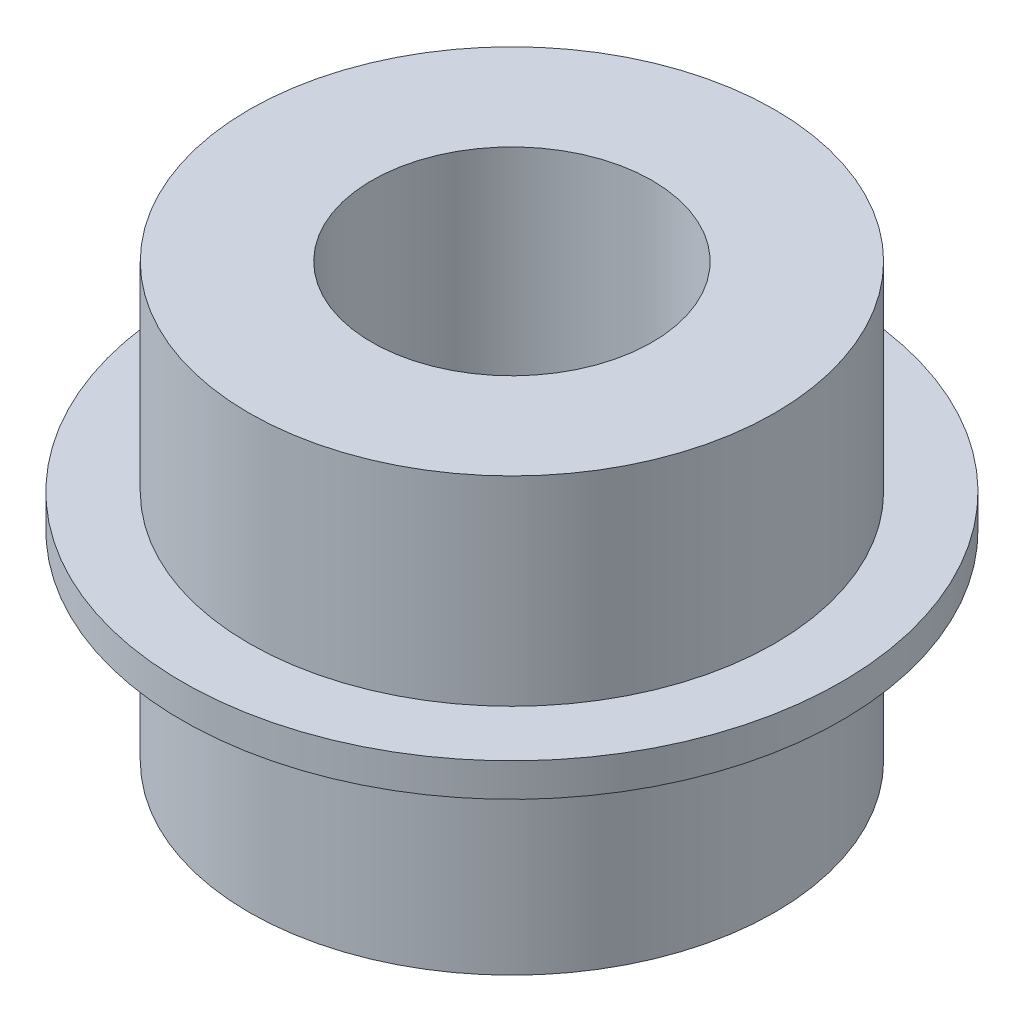
SolidWorks part; units mm, degrees
ref_plane "Front Plane" through (0, 0, 0) normal (0, 0, 1) x (1, 0, 0)
ref_plane "Top Plane" through (0, 0, 0) normal (0, 1, 0) x (1, 0, 0)
ref_plane "Right Plane" through (0, 0, 0) normal (1, 0, 0) x (0, 0, -1)
sketch "Sketch1" plane through (0, 0, 0) normal (0, 0, 1) x (1, 0, 0)
  line L0 (-4.2, -6.477) -> (-4.2, 6.477)
  line L13 (-4.2, 6.477) -> (-7.874, 6.477)
  line L14 (-7.874, 6.477) -> (-7.874, 0.5)
  line L15 (-7.874, 0.5) -> (-9.874, 0.5)
  line L16 (-9.874, 0.5) -> (-9.874, -0.5)
  line L17 (-9.874, -0.5) -> (-7.874, -0.5)
  line L18 (-7.874, -0.5) -> (-7.874, -6.477)
  line L19 (-7.874, -6.477) -> (-4.2, -6.477)
  line L20 (0, 0) -> (0, 9.5041) construction
  point P10 (-4.2, 0)
  dimension "D1" = 4.2
  dimension "D2" = 7.874
  dimension "D3" = 1
  dimension "D4" = 12.954
  dimension "D5" = 2
revolve "Revolve1" add sketch "Sketch1" angle 360 about L20
move or copy body "Body-Convert to Mesh Body1" [suppressed] bodies to move or copy 101 copy no translate (0, 0, 0)
